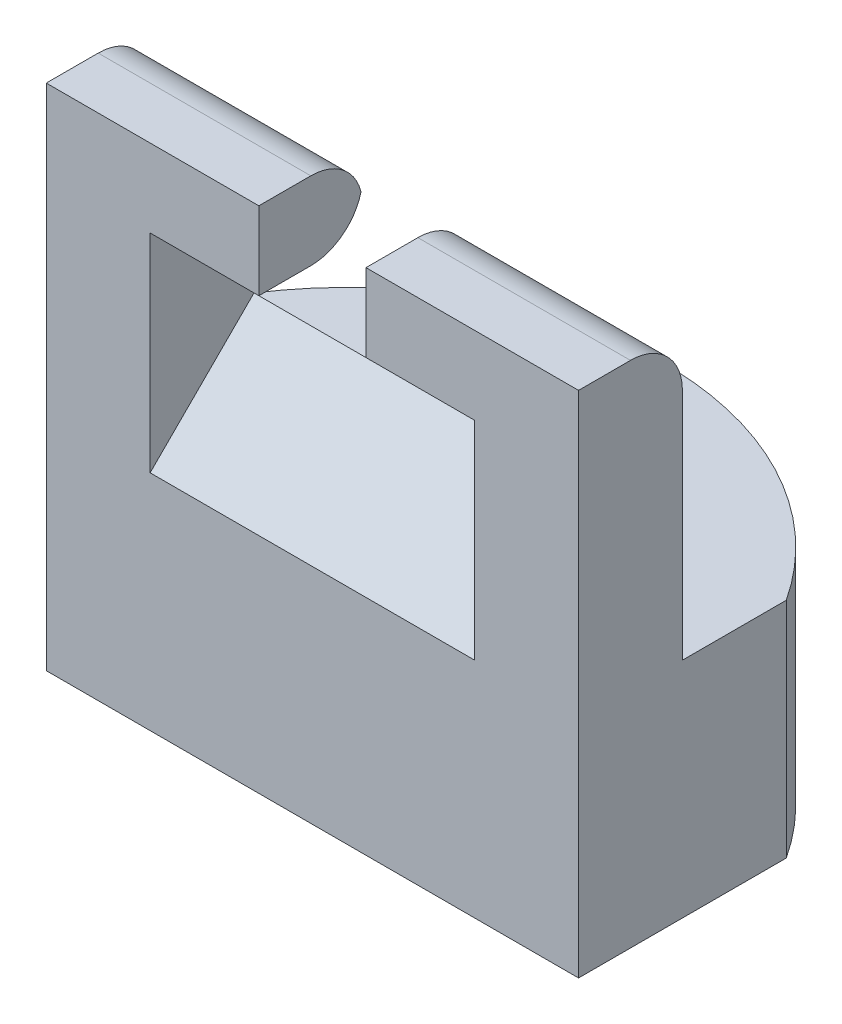
SolidWorks part; units mm, degrees
ref_plane "Front Plane" through (0, 0, 0) normal (0, 0, 1) x (1, 0, 0)
ref_plane "Top Plane" through (0, 0, 0) normal (0, 1, 0) x (1, 0, 0)
ref_plane "Right Plane" through (0, 0, 0) normal (1, 0, 0) x (0, 0, -1)
sketch "Sketch1" plane through (0, 0, 0) normal (0, 1, 0) x (1, 0, 0)
  line L17 (10.25, 4) -> (10.25, 0)
  line L21 (0, 4) -> (0, 0)
  line L23 (0, 0) -> (10.25, 0)
  arc A1 (0, 4) -> (10.25, 4) centre (5.125, 0.6459) cw
  dimension "D2" = 12.25
  dimension "D4" = 4
  dimension "D1" = 10.25
extrude "ProfileBoss-Extrude1" add sketch "Sketch1" along normal blind 4.3
sketch "AngleSketch7" plane through (0, 4.3, 0) normal (0, 1, 0) x (1, 0, 0)
  line L9 (10.25, 0) -> (10.25, 2)
  line L12 (5.2015, -4.929) -> (3.2015, -4.929) construction
  line L24 (0, 0) -> (0, 2)
  line L25 (0, 2) -> (10.25, 2)
  line L28 (0, 0) -> (10.25, 0)
  line L29 (0, 4) -> (0, 0) construction
  line L33 (0, 0) -> (10.25, 0) construction
extrude "AngleBoss-Extrude3" add sketch "AngleSketch7" along normal blind 5.5
sketch "UnderRollerSketch10" plane through (0, 0, 0) normal (0, 0, 1) x (1, 0, 0)
  line L0 (10.25, 9.8) -> (10.25, 0) construction
  line L1 (2, 8.3) -> (8.25, 8.3)
  line L2 (2, 8.3) -> (2, 6.3)
  line L3 (2, 6.3) -> (8.25, 6.3)
  line L4 (8.25, 8.3) -> (8.25, 6.3)
  line L5 (0, 0) -> (10.25, 0) construction
  line L6 (0, 9.8) -> (0, 0) construction
  line L7 (10.25, 9.8) -> (10.25, 0) construction
  line L8 (0, 9.8) -> (10.25, 9.8) construction
  dimension "D1" = 2
  dimension "D3" = 2
  dimension "D4" = 1.5
extrude "UnderRollerCut-Extrude5" cut sketch "UnderRollerSketch10" against normal through all
fillet "UnderFillet22" radius 1 1 edges at (5.125, 8.3, -2)
sketch "Sketch2" plane through (0, 9.8, 0) normal (0, 1, 0) x (1, 0, 0)
  line L0 (10.25, 2) -> (0, 2) construction
  line L1 (4.0938, 2) -> (6.1562, 2)
  line L2 (4.0938, 2) -> (4.0938, 0)
  line L3 (4.0938, 0) -> (6.1562, 0)
  line L4 (6.1562, 2) -> (6.1562, 0)
  line L5 (0, 0) -> (10.25, 0) construction
  line L6 (0, 2) -> (0, 0) construction
  line L7 (10.25, 0) -> (10.25, 2) construction
  dimension "D1" = 4.0938
  dimension "D2" = 2.0625
  dimension "D3" = 4.0937
  dimension "D4" = 10.25
extrude "OpenningCut-Extrude1" cut sketch "Sketch2" against normal up to next
chamfer "OutChamfer1" distance 2 angle 45 1 edges at (5.125, 6.3, 0)
fillet "TopFillet1" radius 1 1 edges at (2.0469, 9.8, -2)
sketch "ClampMountHoleSketch3" plane through (0, 0, 0) normal (0, -1, 0) x (1, 0, 0)
  line L0 (0, -4) -> (0, 0) construction
  circle A0 centre (5.125, -4) radius 2.05
  dimension "D2" = 5.125
extrude "Cut-Extrude1" cut sketch "ClampMountHoleSketch3" against normal blind 4.1
equation "\"RibbonCableWidth\"= 5.25mm"
equation "\"M2.5HeatInsertHoleDiameter\"= 4mm + .1mm'Add  .1mm for printing"
equation "\"ClampBridgeWidth\"= 2mm"
equation "\"ClampWidth\"= \"RibbonCableHoleWidth\" + \"ClampBridgeWidth\" * 2"
equation "\"ClampBridgeHeight\"= 5.5mm"
equation "\"BaseBoss\"= \"M2.5HeatInsertDepth\" + .2mm'Add .2mm to cover mounting hole"
equation "\"D1@ProfileBoss-Extrude1\"=\"BaseBoss\""
equation "\"D1@AngleBoss-Extrude3\"=\"ClampBridgeHeight\" "
equation "\"D1@UnderRollerSketch10\" = \"ClampBridgeWidth\""
equation "\"D1\"= \"ClampBridgeWidth\""
equation "\"D4@Sketch1\"=\"ClampBridgeWidth\"*2"
equation "\"RibbonCableLowerWallHeight\"= 2mm"
equation "\"D2@AngleSketch7\"=\"ClampBridgeWidth\""
equation "\"D1@OutChamfer1\"=\"RibbonCableLowerWallHeight\""
equation "\"D3@UnderRollerSketch10\"=\"ClampBridgeWidth\""
equation "\"D2@Sketch2\"=\"RibbonCableHoleWidth\" *.33"
equation "\"D1@Sketch2\"=(\"ClampWidth\" - \"RibbonCableHoleWidth\" *.33)/2"
equation "\"RibbonCableHoleWidth\"= \"RibbonCableWidth\" + 1mm"
equation "\"D2@Sketch1\"=\"ClampWidth\" + \"ClampBridgeWidth\""
equation "\"M2.5HeatInsertDepth\"= 4.1mm'Spec"
equation "\"D1@Sketch1\"=\"ClampWidth\""
equation "\"D1@ClampMountHoleSketch3\" = \"M2.5HeatInsertHoleDiameter\""
equation "\"D2@ClampMountHoleSketch3\" = \"ClampWidth\" / 2"
equation "\"D1@Cut-Extrude1\"=\"M2.5HeatInsertDepth\""
